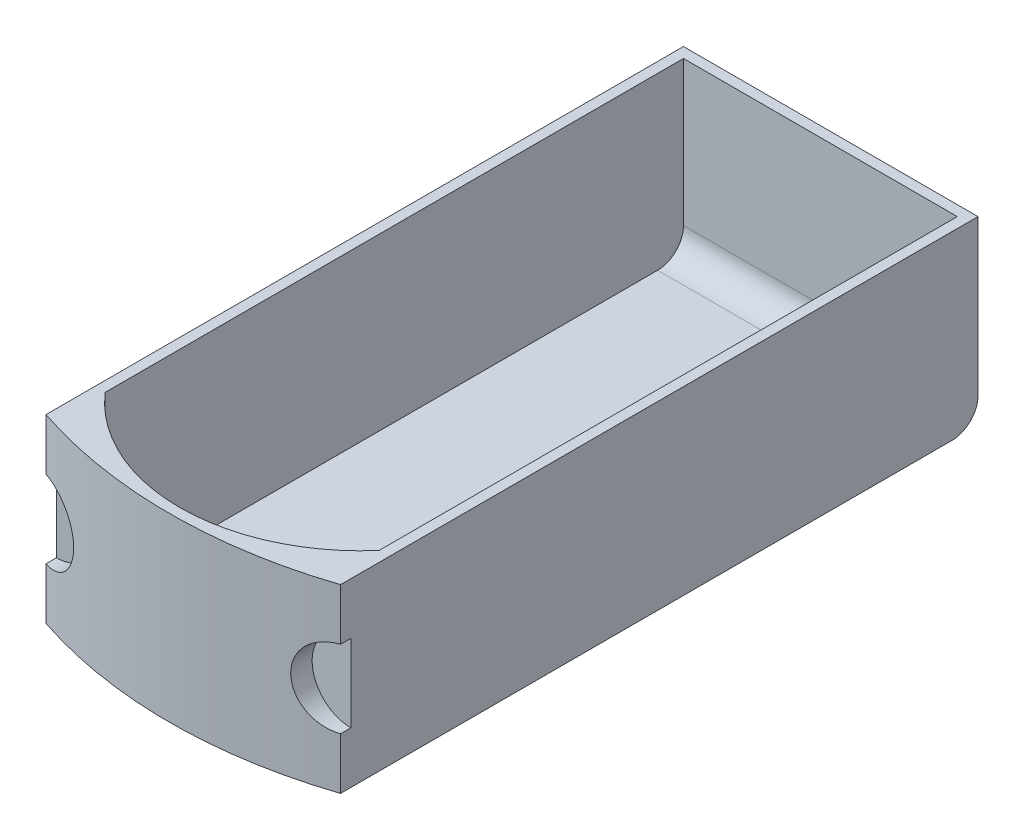
SolidWorks part; units mm, degrees
material "ABS"
ref_plane "Plano frontal" through (0, 0, 0) normal (0, 0, 1) x (1, 0, 0)
ref_plane "Plano superior" through (0, 0, 0) normal (0, 1, 0) x (1, 0, 0)
ref_plane "Plano direito" through (0, 0, 0) normal (1, 0, 0) x (0, 0, -1)
sketch "Esboço2" plane through (0, 0, 0) normal (0, 1, 0) x (1, 0, 0)
  line L0 (0, 0) -> (0, -90) construction
  line L1 (0, 0) -> (0, 38) construction
  line L2 (-81.5843, 38) -> (81.5843, 38) construction
  line L3 (-28.5, 38) -> (-28.5, -85.3683) construction
  line L4 (28.5, 38) -> (28.5, -85.3683) construction
  line L5 (-28.5, -23.6842) -> (28.5, -23.6842) construction
  line L6 (-28.5, -85.3683) -> (-28.5, 38)
  line L7 (-28.5, 38) -> (28.5, 38)
  line L8 (28.5, 38) -> (28.5, -85.3683)
  circle A0 centre (0, 0) radius 90 construction
  arc A1 (-28.5, -85.3683) -> (28.5, -85.3683) centre (0, 0) ccw
  dimension "D1" = 180
  dimension "D2" = 38
  dimension "D3" = 57
extrude "Ressalto-extrusão1" add sketch "Esboço2" along normal blind 35
ref_plane "Plano1" through (0, 0, 85.3683) normal (0, 0, -1) x (-1, 0, 0)
sketch "Esboço3" plane through (0, 0, 85.3683) normal (0, 0, -1) x (-1, 0, 0)
  line L0 (28.5, 35) -> (28.5, 0) construction
  line L1 (-28.5, 35) -> (-28.5, 0) construction
  line L2 (28.5, 35) -> (28.5, 0) construction
  line L3 (-28.5, 35) -> (-28.5, 0) construction
  circle A0 centre (28.5, 17.5) radius 7.5
  circle A1 centre (-28.5, 17.5) radius 7.5
  dimension "D1" = 15
extrude "Corte-extrusão1" cut sketch "Esboço3" against normal up to next and the other way blind 2
shell "Casca1" thickness 2 removed face at (0, 35, 24.8421)
sketch "Esboço4" plane through (0, 35, 0) normal (0, 1, 0) x (1, 0, 0)
  line L0 (26.5, -83.9151) -> (26.5, 36) construction
  line L1 (-26.5, 36) -> (-26.5, -83.9151) construction
  line L2 (26.5, -83.9151) -> (26.5, 36) construction
  line L3 (-26.5, 36) -> (-26.5, -83.9151) construction
  line L4 (26.5, -75.9151) -> (26.5, -83.9151)
  line L5 (-26.5, -75.9151) -> (-26.5, -83.9151)
  arc A0 (-26.5, -83.9151) -> (26.5, -83.9151) centre (0, 0) ccw construction
  arc A1 (-26.5, -83.9151) -> (26.5, -83.9151) centre (0, 0) ccw
  arc A2 (-26.5, -75.9151) -> (26.5, -75.9151) centre (0, -52.9026) ccw
  line M1 (-26.5, 36) -> (26.5, 36)
  line M2 (26.5, 36) -> (26.5, -83.9151)
  arc M3 (26.5, -83.9151) -> (-26.5, -83.9151) centre (0, 0) cw
  line M4 (-26.5, -83.9151) -> (-26.5, 36)
  dimension "D1" = 8
extrude "Ressalto-extrusão3" add sketch "Esboço4" against normal up to surface (33 mm away) contours A2 A1 M4 | A2 M3 M2 region at (-20.25, 35, 83.2159) region at (20.25, 35, 83.2159) up to face at (0, 2, 24.9788)
sketch "Esboço5" plane through (-26.5, 0, 0) normal (-1, 0, 0) x (0, 0, 1)
  line L0 (83.3683, 24.7284) -> (83.3683, 10.2716) construction
  line L1 (83.3683, 24.7284) -> (83.3683, 10.2716)
  line L2 (83.3683, 10.2716) -> (86.3683, 10.2716)
  line L3 (86.3683, 10.2716) -> (86.3683, 24.7284)
  line L4 (86.3683, 24.7284) -> (83.3683, 24.7284)
  dimension "D1" = 3
extrude "Corte-extrusão4" cut sketch "Esboço5" against normal up to surface up to face at (-25.8837, 17.5817, 84.4636)
sketch "Esboço6" plane through (26.5, 0, 0) normal (1, 0, 0) x (0, 0, -1)
  line L0 (-83.3683, 10.2716) -> (-83.3683, 24.7284) construction
  line L1 (-83.3683, 10.2716) -> (-83.3683, 24.7284)
  line L2 (-83.3683, 24.7284) -> (-86.3683, 24.7284)
  line L3 (-86.3683, 24.7284) -> (-86.3683, 10.2716)
  line L4 (-86.3683, 10.2716) -> (-83.3683, 10.2716)
  dimension "D1" = 3
extrude "Corte-extrusão5" cut sketch "Esboço6" against normal up to surface up to face at (25.8837, 17.4183, 84.4636)
extrude "Corte-extrusão6" cut sketch "Esboço4<5>" against normal up to surface (33 mm away) contours A2 M2 M1 M4 region at (0, 35, 24.1991) up to face at (0, 2, 22.9788)
sketch "Esboço4<5>" plane through (0, 35, 0) normal (0, 1, 0) x (1, 0, 0) same geometry as "Esboço4"
fillet "Filete1" radius 5 2 edges at (0, 0, -38) (0, 2, -36)
